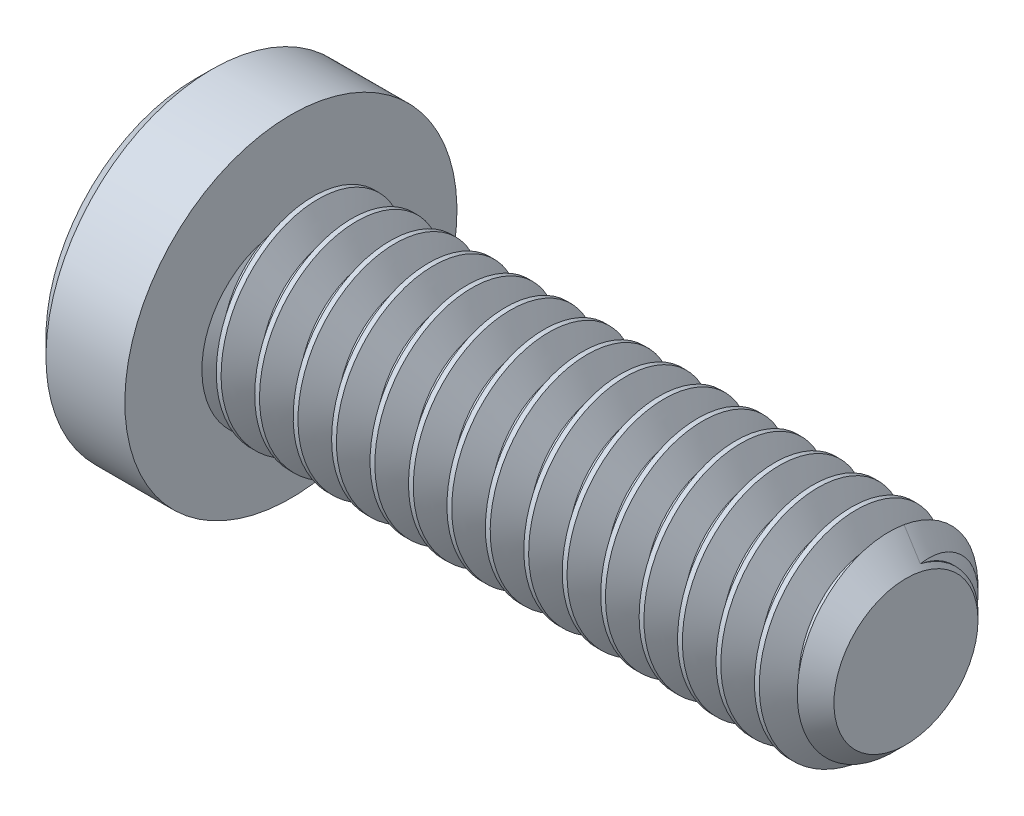
SolidWorks part; units mm, degrees
ref_plane "Front Plane" through (0, 0, 0) normal (0, 0, 1) x (1, 0, 0)
ref_plane "Top Plane" through (0, 0, 0) normal (0, 1, 0) x (1, 0, 0)
ref_plane "Right Plane" through (0, 0, 0) normal (1, 0, 0) x (0, 0, -1)
sketch "Sketch1" plane through (0, 0, 0) normal (0, 0, 1) x (1, 0, 0)
  line L0 (6.35, 0) -> (-6.35, 0) construction
  line L1 (6.35, 2.0828) -> (6.35, -2.0828) construction
  line L2 (-6.35, 3.429) -> (-6.35, -3.429) construction
  line L3 (-6.35, 3.429) -> (-7.9788, 3.429) construction
  line L4 (-7.9788, 3.429) -> (-8.3344, 3.0734) construction
  line L5 (-8.3344, 3.0734) -> (-8.3344, -3.0734) construction
  line L6 (-8.3344, -3.0734) -> (-7.9788, -3.429) construction
  line L7 (-7.9788, -3.429) -> (-6.35, -3.429) construction
  point P7 (-6.8104, 0)
  point P12 (3.175, -2.0828)
  dimension "D1" = 45
  dimension "D2" = 3.175
  dimension "Dec." = 4.1656
  dimension "Length" = 12.7
  dimension "Head Dia" = 6.858
  dimension "Head Height" = 1.9844
  dimension "Hex Depth" = 1.524
  dimension "Chamfer" = 0.3556
ref_plane "Plane1" through (6.35, 0, 0) normal (1, 0, 0) x (0, 0, -1)
ref_plane "Plane2" through (-8.3344, 0, 0) normal (1, 0, 0) x (0, 0, -1)
sketch "Sketch2" plane through (6.35, 0, 0) normal (1, 0, 0) x (0, 0, -1)
  circle A0 centre (0, 0) radius 2.0828
extrude "Boss-Extrude1" add sketch "Sketch2" against normal up to vertex (12.7 mm away) up to point (-6.35, 0, 0)
sketch "Sketch3" plane through (6.35, 0, 0) normal (1, 0, 0) x (0, 0, -1)
  circle A0 centre (0, 0) radius 2.0828 construction
  circle A1 centre (0, 0) radius 2.0828
curve "Helix/Spiral1" pitch 0.7937 height 13.4937 radius 2.0828 centre (6.35, 0, 0) axis (-1, 0, 0) start towards (0, 1, 0) parameters "Pitch"=0.7937
chamfer "Chamfer1" distance 0.5953 angle 45 1 edges at (6.35, 0, -2.0828)
sketch "Sketch5" plane through (0, 0, 0) normal (0, 0, 1) x (1, 0, 0)
  line L0 (6.0027, 2.0828) -> (6.6973, 2.0828)
  line L1 (6.6973, 2.0828) -> (6.3996, 1.5672)
  line L2 (6.3996, 1.5672) -> (6.3004, 1.5672)
  line L3 (6.3004, 1.5672) -> (6.0027, 2.0828)
  line L4 (6.35, 1.5672) -> (6.35, 2.0828) construction
  line L5 (6.1516, 1.825) -> (6.5484, 1.825) construction
  dimension "D1" = 60
  dimension "D2" = 0.3969
  dimension "D3" = 0.0992
sweep "Cut-Sweep1" cut profiles "Sketch5" path "Helix/Spiral1"
sketch "Sketch4" plane through (-8.3344, 0, 0) normal (1, 0, 0) x (0, 0, -1)
  line L0 (-3.429, 0.7937) -> (3.429, 0.7937) construction
  line L1 (0, 1.1457) -> (-0.9922, 0.5728)
  line L2 (-0.9922, 0.5728) -> (-0.9922, -0.5728)
  line L3 (-0.9922, -0.5728) -> (0, -1.1457)
  line L4 (0, -1.1457) -> (0.9922, -0.5728)
  line L5 (0.9922, -0.5728) -> (0.9922, 0.5728)
  line L6 (0.9922, 0.5728) -> (0, 1.1457)
  line L7 (0, 0) -> (0, 0.7937) construction
  circle A0 centre (0, 0) radius 0.9922 construction
  dimension "D1" = 6.858
  dimension "Hex Size" = 1.9844
  dimension "D2" = 0.7937
sketch "Sketch6" plane through (0, 0, 0) normal (0, 0, 1) x (1, 0, 0)
  line L0 (-7.9788, 3.429) -> (-8.3344, 3.0734) construction
  line L1 (-6.35, 3.429) -> (-7.9788, 3.429) construction
  line L2 (-6.35, 3.429) -> (-6.35, -3.429) construction
  line L3 (-8.3344, 3.0734) -> (-8.3344, -3.0734) construction
  line L4 (-7.9788, 3.429) -> (-8.3344, 3.0734)
  line L5 (-6.35, 3.429) -> (-7.9788, 3.429)
  line L6 (-6.35, 3.429) -> (-6.35, 0)
  line L7 (-8.3344, 3.0734) -> (-8.3344, 0)
  line L8 (-6.35, 0) -> (-8.3344, 0) construction
  line L9 (-6.35, 0) -> (-8.3344, 0)
revolve "Revolve1" add sketch "Sketch6" angle 360 about L8
extrude "Cut-Extrude1" cut sketch "Sketch4" along normal up to vertex (1.524 mm away) up to point (-6.8104, 0, 0)
sketch "Sketch8" plane through (-8.3344, 0, 0) normal (-1, 0, 0) x (0, 0, 1)
  circle A1 centre (0, 0) radius 1.1457
extrude "Cut-Extrude2" cut sketch "Sketch8" against normal through all draft 45
equation "\"D3@Helix/Spiral1\" = \"Length@Sketch1\"+\"Pitch@Helix/Spiral1\""
equation "\"D3@Sketch5\" = \"Pitch@Helix/Spiral1\"*.125"
equation "\"D2@Sketch5\" = \"Pitch@Helix/Spiral1\"*.50"
equation "\"D1@Chamfer1\" = \"Pitch@Helix/Spiral1\"*.75"
equation "\"D2@Sketch1\" = \"Pitch@Helix/Spiral1\"*4"
equation "\"D1@Sketch4\" = \"Head Dia@Sketch1\""
